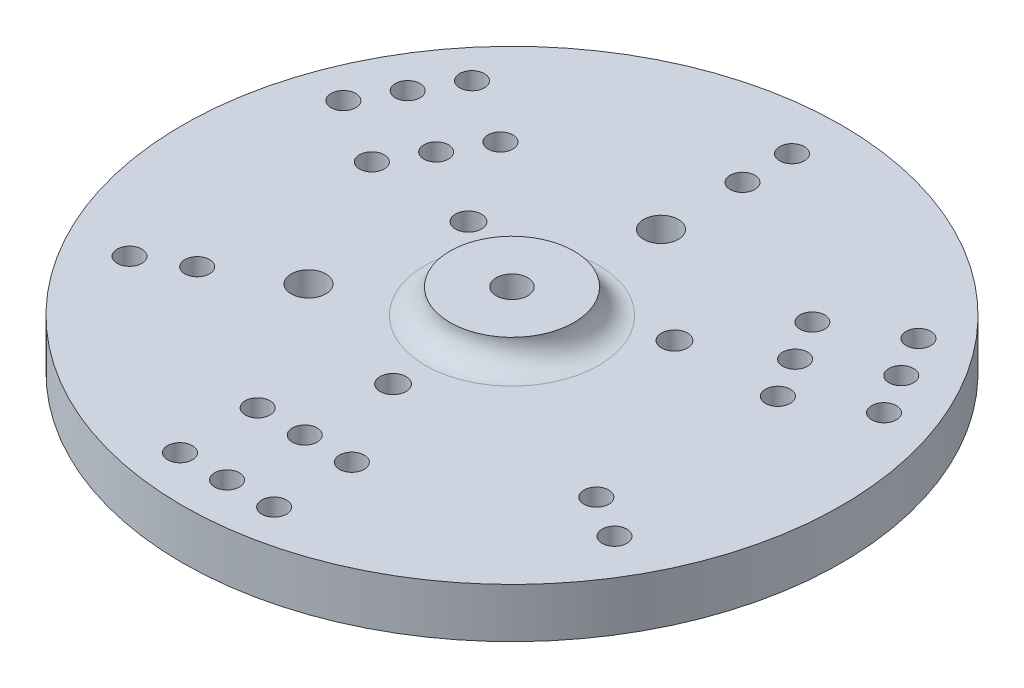
SolidWorks part; units mm, degrees
material "Custom Plastic"
ref_plane "Front Plane" through (0, 0, 0) normal (0, 0, 1) x (1, 0, 0)
ref_plane "Top Plane" through (0, 0, 0) normal (0, 1, 0) x (1, 0, 0)
ref_plane "Right Plane" through (0, 0, 0) normal (1, 0, 0) x (0, 0, -1)
ref_plane "Plane1" through (0, 75, 0) normal (0, 1, 0) x (1, 0, 0)
sketch "Sketch1" plane through (0, 0, 0) normal (0, 1, 0) x (1, 0, 0)
  line L0 (0, 0) -> (0, -65) construction
  line L1 (67.5, 0) -> (-65, 0) construction
  line L2 (-55.608, 32.1053) -> (-46.9587, 47.0864)
  line L3 (0, 0) -> (56.2917, 32.5) construction
  line L4 (0, 0) -> (-56.2917, 32.5) construction
  line L5 (-46.9587, 47.0864) -> (-64.2574, 17.1242)
  line L6 (-53.108, 36.4354) -> (-58.108, 27.7752)
  line L7 (-58.108, 27.7752) -> (-39.4712, 17.0152)
  line L8 (0, -64.2106) -> (-17.2987, -64.2106)
  line L9 (-17.2987, -64.2106) -> (17.2987, -64.2106)
  line L10 (-39.4712, 17.0152) -> (-34.4712, 25.6755)
  line L11 (-58.108, 27.7752) -> (-58.6249, 28.0736)
  line L12 (-53.108, 36.4354) -> (-34.4712, 25.6755)
  line L13 (-50.608, 40.7656) -> (-51.9358, 41.5322)
  line L14 (-60.608, 23.4451) -> (-61.9358, 24.2117)
  line L15 (-50.608, 40.7656) -> (-27.6411, 27.5056) construction
  line L16 (-37.6411, 10.1851) -> (-27.6411, 27.5056) construction
  line L17 (-60.608, 23.4451) -> (-37.6411, 10.1851) construction
  line L18 (55.608, 32.1053) -> (64.2574, 17.1242)
  line L19 (64.2574, 17.1242) -> (46.9587, 47.0864)
  line L20 (58.108, 27.7752) -> (53.108, 36.4354)
  line L21 (53.108, 36.4354) -> (34.4712, 25.6755)
  line L22 (34.4712, 25.6755) -> (39.4712, 17.0152)
  line L23 (53.108, 36.4354) -> (53.6249, 36.7338)
  line L24 (58.108, 27.7752) -> (39.4712, 17.0152)
  line L25 (60.608, 23.4451) -> (61.9358, 24.2117)
  line L26 (-5, -64.2106) -> (5, -64.2106)
  line L27 (5, -64.2106) -> (5, -42.6907)
  line L28 (5, -42.6907) -> (-5, -42.6907)
  line L29 (5, -64.2106) -> (5, -64.8074)
  line L30 (-5, -64.2106) -> (-5, -42.6907)
  line L32 (50.608, 40.7656) -> (51.9358, 41.5322)
  line L33 (60.608, 23.4451) -> (37.6411, 10.1851) construction
  line L34 (27.6411, 27.5056) -> (37.6411, 10.1851) construction
  line L35 (50.608, 40.7656) -> (27.6411, 27.5056) construction
  line L58 (-10, -64.2106) -> (-10, -37.6907) construction
  line L59 (10, -37.6907) -> (-10, -37.6907) construction
  line L60 (10, -64.2106) -> (10, -37.6907) construction
  line L61 (-10, -64.2106) -> (-10, -65.7438)
  line L62 (10, -64.2106) -> (10, -65.7438)
  line L63 (10, -64.2106) -> (10, -64.8074) construction
  circle A0 centre (0, 0) radius 65
  circle A1 centre (0, 0) radius 66.5
  circle A2 centre (0, 0) radius 67
  circle A4 centre (0, 0) radius 4.125
  circle A5 centre (0, 0) radius 11.1125
  point P14 (1.25, 0)
  point P26 (-36.9712, 21.3454)
  point P39 (0, -42.6907)
  point P51 (36.9712, 21.3454)
  point P58 (0, 0)
  point P67 (0, 0)
  point P68 (0, 0)
  point P71 (0, 0)
  point P81 (0, 0)
  dimension "D1" = 130
  dimension "D2" = 133
  dimension "D3" = 35
  dimension "D5" = 30
  dimension "D11" = 8.25
  dimension "D12" = 22.225
  dimension "D8" = 3
  dimension "D9" = 2
  dimension "D10" = 22.3093
  dimension "D4" = 30
  dimension "D7" = 5
  dimension "D6" = 5
extrude "Boss-Extrude7" add sketch "Sketch1" along normal blind 10 separate body contours L5 A1 L9 A0 | L14 A1 L5 A0 | L13 A1 L14 A0 | L5 A1 L13 A0 | L19 A1 L5 A0 | L32 A1 L19 A0 | L25 A1 L32 A0 | L19 A1 L25 A0 | L9 A1 L19 A0 | L9 A1 L61 A0 | L61 A1 L62 A0 | L62 A1 L9 A0 region at (-56.7202, 0, -32.7474) region at (-49.8038, 0, -43.2312) region at (-48.6682, 0, -43.9168) region at (-57.1937, 0, 33.0208) region at (-62.3413, 0, -21.5157) region at (49.8038, 0, -43.2312) region at (-12.5375, 0, 64.747) region at (56.7202, 0, -32.7474) region at (0, 0, 65.4948) region at (62.3413, 0, -21.5157) region at (12.5375, 0, 64.747) region at (64.9042, 0, -8.5)
extrude "Boss-Extrude8" add sketch "Sketch1<23>" along normal blind 10 contours L9 A0 L18 L19 L24 L22 L21 L2 L5 L12 L10 L7 L8 L30 L28 L27 | L11 A0 L14 L5 | L13 A0 L11 L5 L2 | A0 | A4 region at (-55.2563, 0, -33.3861) region at (-50.2707, 0, -37.6841) region at (-59.1838, 0, -26.3345)
sketch "Sketch1<23>" plane through (0, 0, 0) normal (0, 1, 0) x (1, 0, 0) same geometry as "Sketch1"
sketch "Sketch16" plane through (0, 75, 0) normal (0, -1, 0) x (1, 0, 0)
  line L0 (-31.4672, -29.1372) -> (-40.9672, -12.6828)
  line L1 (-45.0465, -36.9772) -> (-54.5465, -20.5228)
  line L2 (-9.5, 57.5) -> (9.5, 57.5)
  line L3 (-9.5, 41.82) -> (9.5, 41.82)
  line L4 (0, 65) -> (0, 0) construction
  line L5 (-65, 0) -> (67.5, 0) construction
  line L11 (54.5465, -20.5228) -> (45.0465, -36.9772)
  line L13 (40.9672, -12.6828) -> (31.4672, -29.1372)
  line L14 (0, 0) -> (56.2917, -32.5) construction
  line L15 (0, 0) -> (-56.2917, -32.5) construction
  circle A2 centre (0, 0) radius 68.75
  circle A3 centre (0, 0) radius 67.5
  circle A4 centre (36.2172, -20.91) radius 2.5
  circle A5 centre (49.7965, -28.75) radius 2.5
  circle A6 centre (-40.9672, -12.6828) radius 2.5
  circle A7 centre (-36.2172, -20.91) radius 2.5
  circle A8 centre (-49.7965, -28.75) radius 2.5
  circle A9 centre (0, 41.82) radius 2.5
  circle A10 centre (0, 57.5) radius 2.5
  circle A11 centre (-31.4672, -29.1372) radius 2.5
  circle A12 centre (-45.0465, -36.9772) radius 2.5
  circle A13 centre (-54.5465, -20.5228) radius 2.5
  circle A14 centre (9.5, 41.82) radius 2.5
  circle A15 centre (-9.5, 41.82) radius 2.5
  circle A16 centre (-9.5, 57.5) radius 2.5
  circle A17 centre (9.5, 57.5) radius 2.5
  circle A18 centre (31.4672, -29.1372) radius 2.5
  circle A19 centre (40.9672, -12.6828) radius 2.5
  circle A20 centre (54.5465, -20.5228) radius 2.5
  circle A21 centre (45.0465, -36.9772) radius 2.5
  point P23 (0, 0)
  point P24 (-36.2172, -20.91)
  point P27 (-49.7965, -28.75)
  point P31 (0, 41.82)
  dimension "D4" = 15.68
  dimension "D5" = 7.5
  dimension "D1" = 137.5
  dimension "D2" = 135
  dimension "D3" = 5
  dimension "D8" = 5
  dimension "D7" = 19
  dimension "D6" = 3
  dimension "D9" = 3
extrude "Cut-Extrude1" cut sketch "Sketch16" along normal blind 20 from surface contours A10 | A9 | A4 | A5 | A7 | A8 | A6 | A13 | A12 | A11 | A15 | A16 | A17 | A14 | A18 | A19 | A20 | A21 starting at face at (0, 10, 66.5)
sketch "Sketch17" plane through (0, 10, 0) normal (0, 1, 0) x (1, 0, 0)
  circle A0 centre (0, 0) radius 12.5
  circle A1 centre (0, 0) radius 3.175
  dimension "D1" = 25
  dimension "D2" = 6.35
extrude "Boss-Extrude9" add sketch "Sketch17" along normal blind 5.5 from offset 0.5 offset against normal yes
fillet "Fillet1" radius 5 1 edges at (0, 10, 12.5)
sketch "Sketch18" plane through (0, 10, 0) normal (0, 1, 0) x (1, 0, 0)
  line L0 (0, 0) -> (0, 66.5) construction
  line L1 (0, 0) -> (57.5907, -33.25)
  line L2 (0, 0) -> (-57.5907, -33.25)
  line L3 (0, 66.5) -> (0, 56.5) construction
  line L4 (0, 56.5) -> (0, 46.5) construction
  circle A0 centre (0, 0) radius 66.5
  circle A1 centre (0, 56.5) radius 2.5
  circle A2 centre (0, 46.5) radius 2.5
  circle A3 centre (48.9304, -28.25) radius 2.5
  circle A4 centre (40.2702, -23.25) radius 2.5
  circle A5 centre (-48.9304, -28.25) radius 2.5
  circle A6 centre (-40.2702, -23.25) radius 2.5
  circle A7 centre (26.0352, -15.0314) radius 3.5
  circle A8 centre (-26.0352, -15.0314) radius 3.5
  circle A9 centre (0, 30.0628) radius 3.5
  point P21 (0, 0)
  point P28 (0, 0)
  dimension "D1" = 133
  dimension "D6" = 5
  dimension "D8" = 7
  dimension "D2" = 120
  dimension "D3" = 120
  dimension "D4" = 10
  dimension "D5" = 10
  dimension "D7" = 3
  dimension "D9" = 3
extrude "Cut-Extrude2" cut sketch "Sketch18" against normal blind 10 contours A1 | A2 | A4 | A3 | A6 | A5 | A8 | A9 region at (0, 10, -56.5) region at (0, 10, -46.5)
sketch "Sketch19" plane through (0, 10, 0) normal (0, 1, 0) x (1, 0, 0)
  line L0 (-18.7038, 57.0377) -> (19.2962, 57.0377)
  line L1 (-30.349, -30.2071) -> (31.651, -30.2071)
  line L2 (-30.349, -30.2071) -> (-30.349, -51.5471)
  line L3 (-30.349, -51.5471) -> (31.651, -51.5471)
  line L4 (31.651, -30.2071) -> (31.651, -51.5471)
  line L5 (-18.7038, 57.0377) -> (-18.7038, 20.0377)
  line L6 (-18.7038, 20.0377) -> (19.2962, 20.0377)
  line L7 (19.2962, 57.0377) -> (19.2962, 20.0377)
  line L24 (-33.349, -30.2071) -> (-33.349, -51.5471)
  line L25 (-30.349, -54.5471) -> (31.651, -54.5471)
  line L26 (-30.349, -27.2071) -> (31.651, -27.2071)
  line L27 (34.651, -30.2071) -> (34.651, -51.5471)
  line L28 (-28.9142, -30.2071) -> (-28.9142, -51.5471)
  line L29 (-30.349, -50.1699) -> (31.651, -50.1699)
  line L30 (30.3321, -51.5471) -> (30.3321, -30.2071)
  line L31 (-30.349, -31.5224) -> (31.651, -31.5224)
  line L32 (-55.871, -13.6613) -> (-55.871, -17.6613)
  line L41 (-37.371, -13.6613) -> (-37.371, -17.6613)
  line L43 (-58.371, -16.1613) -> (-58.371, -17.6613)
  line L44 (-34.871, -16.1613) -> (-34.871, -17.6613)
  line L46 (0, 0) -> (84.871, 0) construction
  line L47 (0, 0) -> (70.727, -40.8342) construction
  line L48 (23.5537, -16.7634) -> (25.1717, -15.5878) construction
  line L49 (24.0705, -12.3707) -> (27.8911, -17.6293) construction
  line L50 (25.1717, -15.5878) -> (26.7898, -14.4122) construction
  line L60 (49.4423, 2.0458) -> (43.3746, -2.3626) construction
  line L61 (53.7037, -3.8196) -> (27.8152, -22.6287)
  line L62 (45.1808, 7.9111) -> (19.2923, -10.898)
  line L63 (28.7001, -17.0415) -> (27.082, -18.2171)
  line L64 (24.8795, -11.7829) -> (23.2614, -12.9585)
  line L65 (31.4557, -19.9837) -> (22.9328, -8.2529)
  line L77 (24.5509, -7.0774) -> (33.0738, -18.8081)
  line L78 (23.2614, -12.9585) -> (27.082, -18.2171)
  line L80 (24.8795, -11.7829) -> (28.7001, -17.0415)
  line L82 (19.2923, -10.898) -> (27.8152, -22.6287)
  line L84 (45.1808, 7.9111) -> (53.7037, -3.8196)
  line L86 (42.7538, 6.1478) -> (51.2766, -5.583)
  line L87 (-59.871, 8.8387) -> (-59.871, -17.6613)
  line L88 (-57.871, 6.8387) -> (-35.371, 6.8387) construction
  line L89 (-57.871, 6.8387) -> (-57.871, -15.6613) construction
  line L90 (-57.871, -15.6613) -> (-35.371, -15.6613) construction
  line L91 (-35.371, 6.8387) -> (-35.371, -15.6613) construction
  line L92 (-59.871, -17.6613) -> (-33.371, -17.6613)
  line L93 (-33.371, 8.8387) -> (-33.371, -17.6613)
  line L94 (-59.871, 8.8387) -> (-33.371, 8.8387)
  line L95 (-58.371, 7.3387) -> (-58.371, -16.1613)
  line L96 (-58.371, -16.1613) -> (-34.871, -16.1613)
  line L97 (-34.871, 7.3387) -> (-34.871, -16.1613)
  line L98 (-58.371, 7.3387) -> (-34.871, 7.3387)
  line L99 (-55.871, 4.8387) -> (-37.371, 4.8387)
  line L100 (-37.371, 4.8387) -> (-37.371, -13.6613)
  line L101 (-55.871, -13.6613) -> (-37.371, -13.6613)
  line L102 (-55.871, 4.8387) -> (-55.871, -13.6613)
  circle A0 centre (-30.349, -30.2071) radius 1.25
  circle A1 centre (-30.349, -51.5471) radius 1.25
  circle A2 centre (31.651, -51.5471) radius 1.25
  circle A3 centre (31.651, -30.2071) radius 1.25
  circle A4 centre (31.651, -30.2071) radius 3
  circle A5 centre (31.651, -51.5471) radius 3
  circle A6 centre (-30.349, -51.5471) radius 3
  circle A7 centre (-30.349, -30.2071) radius 3
  circle A10 centre (-18.7038, 57.0377) radius 1.25
  circle A11 centre (-18.7038, 20.0377) radius 1.25
  circle A12 centre (19.2962, 20.0377) radius 1.25
  circle A13 centre (19.2962, 57.0377) radius 1.25
  circle A14 centre (19.2962, 57.0377) radius 3
  circle A15 centre (19.2962, 20.0377) radius 3
  circle A16 centre (-18.7038, 20.0377) radius 3
  circle A17 centre (-18.7038, 57.0377) radius 3
  circle A23 centre (43.3746, -2.3626) radius 1.25
  circle A24 centre (-57.871, 6.8387) radius 2
  circle A25 centre (-57.871, -15.6613) radius 2
  circle A26 centre (-35.371, -15.6613) radius 2
  circle A27 centre (-35.371, 6.8387) radius 2
  circle A28 centre (25.9808, -15) radius 1.4766
  point P28 (49.4423, 2.0458)
  dimension "D3" = 2.5
  dimension "D4" = 6
  dimension "D5" = 2
  dimension "D6" = 6.5
  dimension "D20" = 30
  dimension "D14" = 2.5
  dimension "D1" = 62
  dimension "D2" = 21.34
  dimension "D7" = 38
  dimension "D8" = 37
  dimension "D9" = 4.5
  dimension "D10" = 6.5
  dimension "D15" = 3
  dimension "D16" = 4
  dimension "D17" = 2
  dimension "D19" = 30
  dimension "D22" = 22.5
  dimension "D23" = 22.5
  dimension "D11" = 14.5
  dimension "D12" = 32
  dimension "D13" = 7.5
sketch "Sketch20" plane through (0, 10, 0) normal (0, 1, 0) x (1, 0, 0)
  line L0 (0, 0) -> (-36.2172, 20.91)
  line L1 (0, 0) -> (36.2172, 20.91)
  line L2 (0, 0) -> (0, -41.82)
  line L3 (-6.5, -28.0056) -> (-12, -14.407)
  line L4 (6.5, -28.0056) -> (12, -14.407)
  line L5 (-21.0035, 19.632) -> (-6.4769, 17.5958)
  line L6 (-27.5035, 8.3736) -> (-18.4769, -3.1888)
  line L7 (27.5035, 8.3736) -> (18.4769, -3.1888)
  line L8 (21.0035, 19.632) -> (6.4769, 17.5958)
  circle A0 centre (0, 0) radius 24
  circle A1 centre (-20.7846, 12) radius 2
  circle A2 centre (20.7846, 12) radius 2
  circle A3 centre (0, -24) radius 2
  circle A4 centre (0, 0) radius 18.75
  circle A5 centre (0, 0) radius 28.75
  circle A6 centre (0, 0) radius 7.5
  circle A7 centre (0, 0) radius 12.5
  circle A8 centre (0, 0) radius 10
  circle A9 centre (0, 0) radius 5.25
  circle A10 centre (-20.7846, 12) radius 2.625
  circle A11 centre (0, -24) radius 2.625
  circle A12 centre (20.7846, 12) radius 2.625
  point P32 (0, 0)
  dimension "D1" = 4
  dimension "D2" = 37.5
  dimension "D3" = 57.5
  dimension "D4" = 48
  dimension "D8" = 10.5
  dimension "D9" = 20
  dimension "D10" = 25
  dimension "D11" = 15
  dimension "D12" = 5.25
  dimension "D5" = 6.5
  dimension "D6" = 12
  dimension "D7" = 3
extrude "Cut-Extrude11" cut sketch "Sketch20" against normal blind 25 contours A10 | A12 | A11
